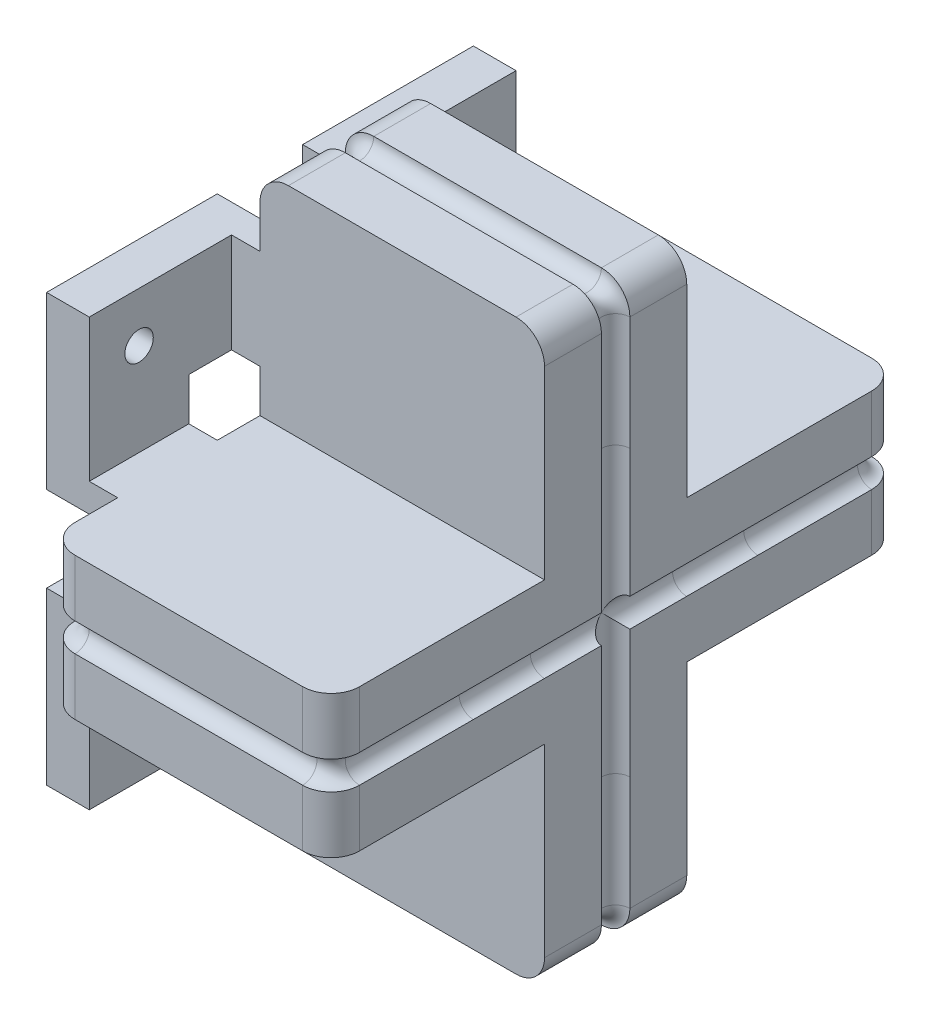
SolidWorks part; units mm, degrees
ref_plane "Front Plane" through (0, 0, 0) normal (0, 0, 1) x (1, 0, 0)
ref_plane "Top Plane" through (0, 0, 0) normal (0, 1, 0) x (1, 0, 0)
ref_plane "Right Plane" through (0, 0, 0) normal (1, 0, 0) x (0, 0, -1)
sketch "Sketch1" plane through (0, 0, 0) normal (0, 0, 1) x (1, 0, 0)
  line L6 (0, 20) -> (0, -20)
  line L8 (10, 10) -> (10, -10)
  line L10 (0, -20) -> (8, -20)
  line L11 (10, -18) -> (10, -10)
  line L12 (10, 10) -> (10, 18)
  line L13 (8, 20) -> (0, 20)
  arc A6 (10, 18) -> (8, 20) centre (8, 18) ccw
  arc A7 (8, -20) -> (10, -18) centre (8, -18) ccw
  dimension "D1" = 8
  dimension "D2" = 2
  dimension "D3" = 40
  dimension "D4" = 10
  dimension "D5" = 20
extrude "Boss-Extrude1" add sketch "Sketch1" along normal mid plane 10 contours L6 L10 A7 L11 L8 L12 A6 L13
sketch "Sketch24" plane through (0, 0, 0) normal (0, 1, 0) x (1, 0, 0)
  line L0 (10, -5) -> (10, 5) construction
  circle A0 centre (10, 0) radius 1
  dimension "D1" = 2
sketch "Sketch25" plane through (0, 0, 0) normal (1, 0, 0) x (0, 0, -1)
  line L0 (0, 20) -> (0, -20) construction
  line L1 (0, 5) -> (20, 5)
  line L2 (0, 5) -> (0, -5)
  line L3 (0, -5) -> (20, -5)
  line L6 (20, 5) -> (20, -5)
  dimension "D1" = 10
  dimension "D2" = 20
sketch "Sketch26" plane through (0, 0, 0) normal (0, 1, 0) x (1, 0, 0)
  line L0 (0, 5) -> (0, 20)
  line L2 (10, 5) -> (10, 10)
  line L5 (0, -5) -> (0, -20)
  line L6 (0, 20) -> (8, 20)
  line L7 (10, -5) -> (10, 5) construction
  line L8 (10, -5) -> (10, -10)
  line L9 (8, -5) -> (0, -5) construction
  line L11 (0, -5) -> (0, 5)
  line L12 (10, 5) -> (10, -5)
  line L13 (10, 18) -> (10, 10)
  line L14 (10, -10) -> (10, -18)
  line L15 (8, -20) -> (0, -20)
  arc A0 (10, -18) -> (8, -20) centre (8, -18) cw
  arc A4 (8, 20) -> (10, 18) centre (8, 18) cw
  dimension "D1" = 40
  dimension "D2" = 20
  dimension "D5" = 2
  dimension "D3" = 10
  dimension "D4" = 10
  dimension "D6" = 5
extrude "Boss-Extrude3" add sketch "Sketch26" along normal mid plane 10 contours L8 L5 | L2 L0 region at (4.9804, 0, 0)
sweep "Cut-Sweep3" cut profiles "Sketch24" path "Sketch1<5>"
sketch "Sketch1<5>" plane through (0, 0, 0) normal (0, 0, 1) x (1, 0, 0) same geometry as "Sketch1"
sketch "Sketch29" plane through (0, 0, 0) normal (0, 0, 1) x (1, 0, 0)
  line L0 (10, 0) -> (10, -10) construction
  line L1 (10, 0) -> (10, -10) construction
  line L2 (10, 10) -> (10, -10) construction
  circle A0 centre (10, 0) radius 1
  point P2 (0, 0)
  point P8 (10, 0)
  point P9 (0, 0)
  point P10 (10, 0)
  dimension "D1" = 2
sweep "Cut-Sweep6" cut profiles "Sketch29" path "Sketch26<7>"
sketch "Sketch26<7>" plane through (0, 0, 0) normal (0, 1, 0) x (1, 0, 0) same geometry as "Sketch26"
mirror "Mirror1" about plane through (0, 0, 0) normal (1, 0, 0) of bodies 111 105
sketch "Sketch27" plane through (0, 0, 0) normal (0, 1, 0) x (1, 0, 0)
  circle A0 centre (0, 0) radius 1
  arc A2 (-1, 0) -> (0, -1) centre (0, 0) ccw construction
extrude "Boss-Extrude7" add sketch "Sketch27" along normal up to surface (20 mm away) up to face at (-3.4828, 19.5172, 0)
sketch "Sketch31" plane through (0, 0, 0) normal (0, 0, 1) x (1, 0, 0)
  circle A0 centre (0, 0) radius 1
  dimension "D1" = 2
extrude "Boss-Extrude10" add sketch "Sketch31" along normal up to surface and the other way up to surface up to face at (3.4828, 0, 19.5172) other way up to face at (4.25, 0, -19.5)
sketch "Sketch32" plane through (0, 0, 0) normal (0, 1, 0) x (1, 0, 0)
  circle A0 centre (0, 0) radius 1
  dimension "D1" = 2
extrude "Boss-Extrude11" add sketch "Sketch32" against normal up to surface (20 mm away) up to face at (4.25, -19.5, 0)
sketch "Sketch34" plane through (-10, 0, 0) normal (-1, 0, 0) x (0, 0, 1)
  line L0 (5, -5) -> (18, -5) construction
  line L1 (15, -5) -> (8, -5)
  line L2 (15, -5) -> (15, -3)
  line L3 (15, -3) -> (8, -3)
  line L4 (8, -5) -> (8, -3)
  line L5 (5, -18) -> (5, -5) construction
  line L6 (5, -15) -> (3, -15)
  line L7 (5, -15) -> (5, -8)
  line L8 (5, -8) -> (3, -8)
  line L9 (3, -15) -> (3, -8)
  line L10 (11, 0) -> (-11, 0) construction
  line L11 (15, 3) -> (8, 3)
  line L12 (8, 5) -> (8, 3)
  line L13 (15, 5) -> (8, 5)
  line L14 (15, 5) -> (15, 3)
  line L15 (0, -11) -> (0, 11) construction
  line L16 (-5, -8) -> (-3, -8)
  line L17 (-3, -15) -> (-3, -8)
  line L18 (-5, -15) -> (-3, -15)
  line L19 (-5, -15) -> (-5, -8)
  line L20 (-15, -3) -> (-8, -3)
  line L21 (-8, -5) -> (-8, -3)
  line L22 (-15, -5) -> (-8, -5)
  line L23 (-15, -5) -> (-15, -3)
  line L24 (-15, 5) -> (-15, 3)
  line L25 (-15, 5) -> (-8, 5)
  line L26 (-8, 5) -> (-8, 3)
  line L27 (-15, 3) -> (-8, 3)
  line L28 (-5, 15) -> (-5, 8)
  line L29 (-5, 15) -> (-3, 15)
  line L30 (-3, 15) -> (-3, 8)
  line L31 (-5, 8) -> (-3, 8)
  line L32 (5, 8) -> (3, 8)
  line L33 (3, 15) -> (3, 8)
  line L34 (5, 15) -> (3, 15)
  line L35 (5, 15) -> (5, 8)
  point P12 (11.5, -5)
  point P13 (5, -11.5)
  dimension "D1" = 7
  dimension "D2" = 2
extrude "Boss-Extrude12" add sketch "Sketch34" along normal blind 5
sketch "Sketch35" plane through (-15, 0, 0) normal (-1, 0, 0) x (0, 0, 1)
  line L0 (-5, -8) -> (-8, -8)
  line L1 (8, -5) -> (15, -5)
  line L2 (8, -5) -> (8, -8)
  line L3 (8, -15) -> (15, -15)
  line L4 (15, -5) -> (15, -15)
  line L5 (-5, -15) -> (-15, -15)
  line L6 (-5, -8) -> (-5, -15)
  line L7 (-15, -8) -> (-15, -15)
  line L8 (-8, 5) -> (-8, 8)
  line L9 (-15, 5) -> (-15, 15)
  line L10 (-8, 5) -> (-15, 5)
  line L11 (-8, 15) -> (-15, 15)
  line L12 (5, 8) -> (8, 8)
  line L13 (5, 15) -> (15, 15)
  line L14 (5, 8) -> (5, 15)
  line L15 (15, 8) -> (15, 15)
  line L16 (0, 0) -> (8, -5) construction
  line L17 (5, 8) -> (5, 15) construction
  line L18 (-5, 8) -> (-8, 8)
  line L19 (-8, 15) -> (-5, 15)
  line L20 (-5, 15) -> (-5, 8)
  line L21 (8, 5) -> (8, 8)
  line L22 (15, 5) -> (8, 5)
  line L23 (15, 8) -> (15, 5)
  line L24 (5, -8) -> (8, -8)
  line L25 (5, -15) -> (5, -8)
  line L26 (8, -15) -> (5, -15)
  line L27 (-8, -5) -> (-8, -8)
  line L28 (-15, -5) -> (-8, -5)
  line L29 (-15, -8) -> (-15, -5)
  dimension "D1" = 10
  dimension "D3" = 9.434
  dimension "D2" = 4
extrude "Boss-Extrude13" add sketch "Sketch35" against normal blind 3
sketch "Sketch36" plane through (-12, 0, 0) normal (1, 0, 0) x (0, 0, -1)
  line L2 (-15, -15) -> (-8, -8) construction
  line L3 (0, 0) -> (-11.5, -11.5) construction
  line L4 (15, -15) -> (5, -15) construction
  point P0 (-11.5, -11.5)
  point P1 (0, 0)
  point P5 (0, 0)
  point P14 (-11.5, 11.5)
  point P15 (11.5, 11.5)
  point P16 (11.5, -11.5)
  dimension "D2" = 16.2635
  dimension "D3" = 15
  dimension "D1" = 4
hole_wizard "M1.6 Clearance Hole1" positions "Sketch37" profile "Sketch38" hole size "M1.6" standard "ANSI Metric" end condition through all
sketch "Sketch37" plane through (-12, 0, 0) normal (1, 0, 0) x (0, 0, -1)
  point P0 (-11.5, -11.5)
  point P3 (-11.5, 11.5)
  point P6 (11.5, 11.5)
  point P9 (11.5, -11.5)
sketch "Sketch38" plane through (-12, -11.5, 11.5) normal (0, 1, 0) x (0, 0, -1)
  line L0 (0, 0) -> (0, 3)
  line L1 (0, 3) -> (1, 3)
  line L2 (1, 3) -> (1, 0)
  line L5 (1, 0) -> (0, 0)
  line L11 (0, -6.35) -> (0, 107.95) construction
  dimension "Thru Hole Dia." = 2
  dimension "Thru Hole Depth" = 3
